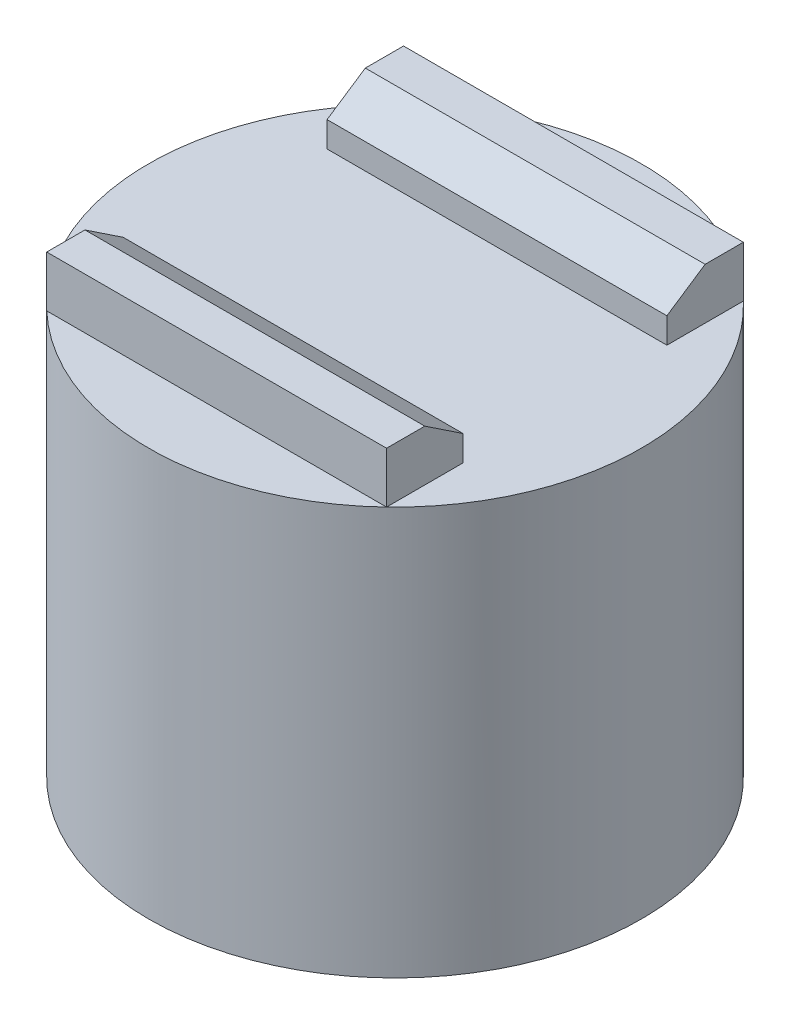
SolidWorks part; units mm, degrees
material "Plain Carbon Steel"
ref_plane "Front Plane" through (0, 0, 0) normal (0, 0, 1) x (1, 0, 0)
ref_plane "Top Plane" through (0, 0, 0) normal (0, 1, 0) x (1, 0, 0)
ref_plane "Right Plane" through (0, 0, 0) normal (1, 0, 0) x (0, 0, -1)
sketch "Sketch1" plane through (0, 0, 0) normal (0, 1, 0) x (1, 0, 0)
  circle A0 centre (0, 0) radius 14.5
  dimension "D1" = 29
extrude "Boss-Extrude1" add sketch "Sketch1" along normal blind 24
sketch "Sketch2" plane through (0, 24, 0) normal (0, 1, 0) x (1, 0, 0)
  line L0 (-21.4304, 0) -> (21.9876, 0) construction
  line L1 (-10, 10.5) -> (10, 10.5)
  line L2 (-10, 10.5) -> (-10, 6)
  line L3 (-10, 6) -> (10, 6)
  line L4 (10, 10.5) -> (10, 6)
  circle A0 centre (0, 0) radius 14.5 construction
  dimension "D1" = 4.5
  dimension "D2" = 20
extrude "Boss-Extrude2" add sketch "Sketch2" along normal blind 3 contours L1 L4 L3 L2
sketch "Sketch3" plane through (10, 0, 0) normal (1, 0, 0) x (0, 0, -1)
  line L0 (6, 25.5) -> (8.25, 27)
  line L1 (6, 27) -> (6, 24) construction
  line L2 (10.5, 27) -> (6, 27) construction
  line L3 (8.25, 27) -> (6, 27)
  line L4 (6, 27) -> (6, 25.5)
extrude "Cut-Extrude1" cut sketch "Sketch3" against normal blind 43
mirror "Mirror1" about plane through (0, 0, 0) normal (0, 0, 1) of bodies 108
sketch "Sketch4" plane through (0, 0, 0) normal (0, -1, 0) x (1, 0, 0)
  circle A0 centre (0, 0) radius 2.5
  dimension "D1" = 5
extrude "Cut-Extrude2" cut sketch "Sketch4" against normal blind 7
